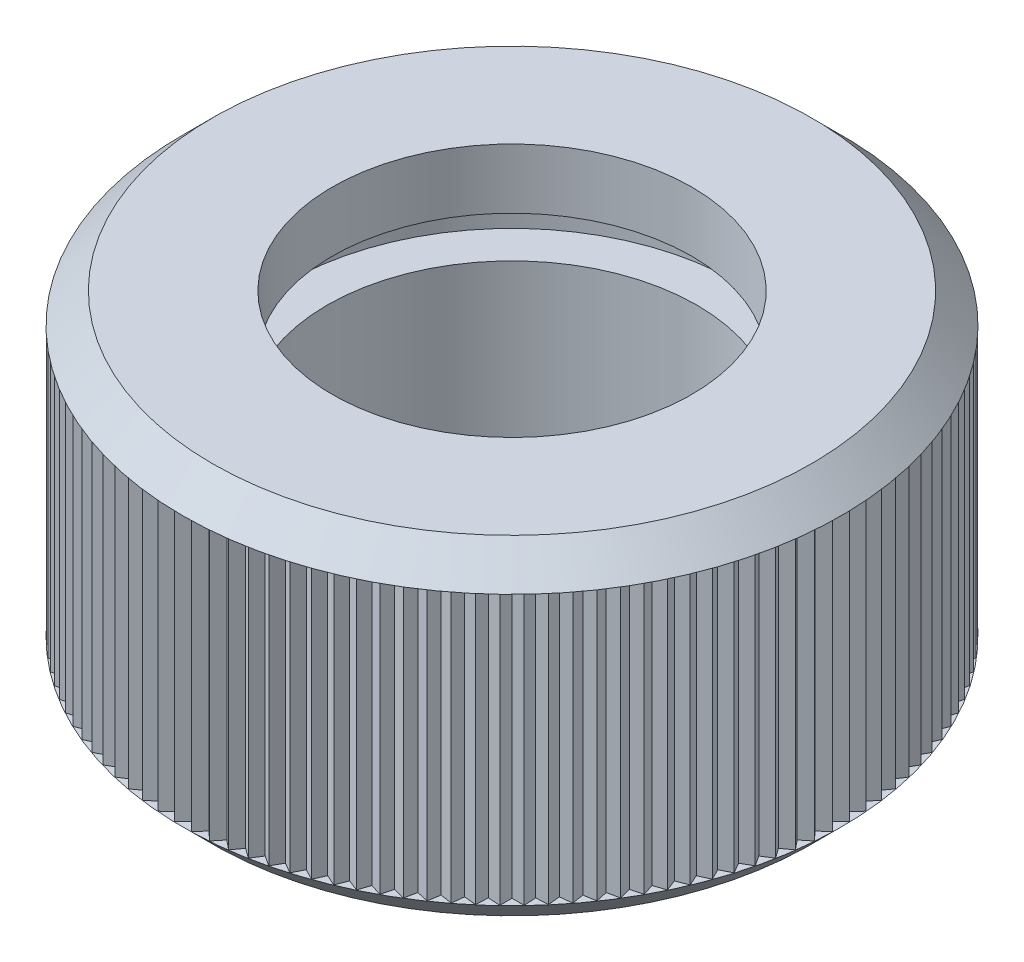
SolidWorks part; units mm, degrees
material "Латунь"
ref_plane "Спереди" through (0, 0, 0) normal (0, 0, 1) x (1, 0, 0)
ref_plane "Сверху" through (0, 0, 0) normal (0, 1, 0) x (1, 0, 0)
ref_plane "Справа" through (0, 0, 0) normal (1, 0, 0) x (0, 0, -1)
sketch "Эскиз1" plane through (0, 0, 0) normal (1, 0, 0) x (0, 0, -1)
  line L0 (6, 11) -> (6, 9)
  line L1 (0, 0) -> (11, 0) construction
  line L2 (0, 0) -> (0, 11) construction
  line L3 (0, 11) -> (11, 11) construction
  line L4 (11, 0) -> (11, 11)
  line L5 (6, 9) -> (7.5, 9)
  line L6 (7.5, 9) -> (7.5, 7.5)
  line L7 (7.5, 7.5) -> (6, 7.5)
  line L8 (6, 7.5) -> (6, 0)
  line L9 (6, 11) -> (11, 11)
  line L10 (6, 0) -> (11, 0)
  dimension "D1" = 11
  dimension "D2" = 11
  dimension "D3" = 6
  dimension "D4" = 1.5
  dimension "D5" = 2
revolve "Повернуть1" add sketch "Эскиз1" angle 360 about L2
chamfer "Фаска1" distance 1 angle 45 2 edges at (0, 0, -11) (0, 11, -11)
ref_plane "Плоскость2" through (0, 5.5, 0) normal (0, 1, 0) x (1, 0, 0)
sketch "Эскиз4" plane through (0, 5.5, 0) normal (0, 1, 0) x (1, 0, 0)
  line L0 (-11, 0) -> (11, 0) construction
  line L1 (-10.6959, 0) -> (-12.6959, 2)
  line L2 (-12.6959, 2) -> (-12.6959, -2)
  line L3 (-12.6959, 0) -> (-10.6959, 0)
  line L4 (-10.6959, 0) -> (-12.6959, -2)
  circle A0 centre (0, 0) radius 11 construction
  point P7 (-10.9959, 0.3)
  dimension "D1" = 45
  dimension "D2" = 0.3
  dimension "D3" = 2
extrude "Вырез-Вытянуть1" cut sketch "Эскиз4" against normal blind 4.5 and the other way blind 4.5 contours L3 L1 | L3 region at (-12.0293, 5.5, -0.6667) region at (-12.0293, 5.5, 0.6667)
pattern_circular "Круговой массив1" count 120 over 360 about axis through (0, 0, 0) along (0, -1, 0) of "Вырез-Вытянуть1"
sketch "Эскиз5" plane through (0, 0, 0) normal (0, -1, 0) x (1, 0, 0)
  circle A0 centre (0, 0) radius 6.172
  dimension "D1" = 12.344
extrude "Вырез-Вытянуть2" cut sketch "Эскиз5" against normal up to surface (9 mm away) up to face at (0, 9, -7.5)
cosmetic thread "Условное изображение резьбы1" parameters "D2"=14
chamfer "Фаска2" distance 0.828 angle 45 1 edges at (0, 0, -6.172)
